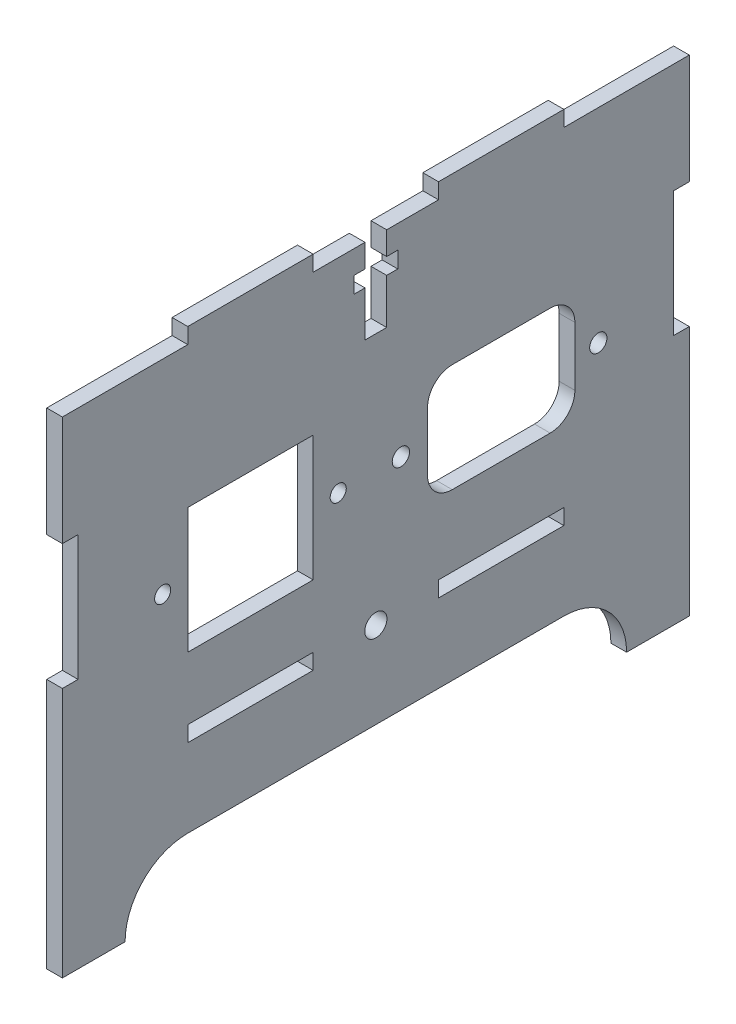
SolidWorks part; units mm, degrees
ref_plane "Front Plane" through (0, 0, 0) normal (0, 0, 1) x (1, 0, 0)
ref_plane "Top Plane" through (0, 0, 0) normal (0, 1, 0) x (1, 0, 0)
ref_plane "Right Plane" through (0, 0, 0) normal (1, 0, 0) x (0, 0, -1)
sketch "Sketch1" plane through (0, 0, 0) normal (1, 0, 0) x (0, 0, -1)
  line L1 (-63.5, 50.8) -> (63.5, 50.8)
  line L2 (-63.5, 50.8) -> (-63.5, -50.8)
  line L3 (-63.5, -50.8) -> (63.5, -50.8)
  line L4 (63.5, 50.8) -> (63.5, -50.8)
  line L5 (-63.5, 50.8) -> (63.5, -50.8) construction
  line L6 (-63.5, -50.8) -> (63.5, 50.8) construction
  point P0 (0, 0)
  dimension "D1" = 127
  dimension "D2" = 101.6
extrude "Boss-Extrude1" add sketch "Sketch1" along normal blind 3.175
sketch "Sketch2" plane through (3.175, 0, 0) normal (1, 0, 0) x (0, 0, -1)
  line L1 (-63.5, 50.8) -> (-38.1, 50.8)
  line L2 (-63.5, 50.8) -> (-63.5, 47.625)
  line L3 (-63.5, 47.625) -> (-38.1, 47.625)
  line L4 (-38.1, 50.8) -> (-38.1, 47.625)
  dimension "D1" = 25.4
  dimension "D2" = 3.175
extrude "Cut-Extrude1" cut sketch "Sketch2" against normal blind 6.35
pattern_linear "LPattern1" count 3 spacing 50.8 along (0, 0, -1) of "Cut-Extrude1"
sketch "Sketch5" plane through (3.175, 0, 0) normal (1, 0, 0) x (0, 0, -1)
  line L0 (-38.1, -50.8) -> (38.1, -50.8) construction
  line L1 (-63.5, -50.8) -> (63.5, -50.8) construction
  line L2 (-38.1, -38.1) -> (38.1, -38.1)
  line L3 (-38.1, -63.5) -> (38.1, -63.5)
  arc A0 (-38.1, -38.1) -> (-38.1, -63.5) centre (-38.1, -50.8) ccw
  arc A1 (38.1, -63.5) -> (38.1, -38.1) centre (38.1, -50.8) ccw
  point P4 (0, -50.8)
  dimension "D2" = 12.7
  dimension "D1" = 76.2
extrude "Cut-Extrude4" cut sketch "Sketch5" against normal blind 6.35
sketch "Sketch8" plane through (3.175, 0, 0) normal (1, 0, 0) x (0, 0, -1)
  line L0 (63.5, -50.8) -> (63.5, 47.625) construction
  line L1 (63.5, 25.4) -> (60.325, 25.4)
  line L2 (63.5, 25.4) -> (63.5, 0)
  line L3 (63.5, 0) -> (60.325, 0)
  line L4 (60.325, 25.4) -> (60.325, 0)
  line L5 (38.1, 50.8) -> (12.7, 50.8) construction
  dimension "D1" = 25.4
  dimension "D2" = 25.4
  dimension "D3" = 3.175
extrude "Cut-Extrude6" cut sketch "Sketch8" against normal blind 6.35
ref_plane "Plane1" through (0, 0, 0) normal (0, 0, 1) x (1, 0, 0)
sketch "Sketch9" plane through (0, 0, 0) normal (-1, 0, 0) x (0, 0, 1)
  line L0 (-63.5, -50.8) -> (-63.5, 0) construction
  line L1 (-38.1, -19.05) -> (-12.7, -19.05)
  line L2 (-38.1, -19.05) -> (-38.1, -22.225)
  line L3 (-38.1, -22.225) -> (-12.7, -22.225)
  line L4 (-12.7, -19.05) -> (-12.7, -22.225)
  line L5 (-38.1, 50.8) -> (-12.7, 50.8) construction
  point P6 (-25.4, 50.8)
  dimension "D1" = 25.4
  dimension "D2" = 3.175
  dimension "D3" = 25.4
  dimension "D4" = 69.85
extrude "Cut-Extrude7" cut sketch "Sketch9" against normal blind 6.35
pattern_linear "LPattern6" count 2 spacing 50.8 along (0, 0, 1) of "Cut-Extrude7"
sketch "Sketch16" plane through (0, 0, 0) normal (-1, 0, 0) x (0, 0, 1)
  line L0 (12.7, 47.625) -> (-12.7, 47.625) construction
  line L1 (-2.1971, 47.625) -> (2.1971, 47.625)
  line L2 (-2.1971, 47.625) -> (-2.1971, 30.48)
  line L3 (-2.1971, 30.48) -> (2.1971, 30.48)
  line L4 (2.1971, 47.625) -> (2.1971, 30.48)
  line L5 (-12.7, 47.625) -> (-12.7, 50.8) construction
  line L7 (-4.445, 42.926) -> (4.445, 42.926)
  line L8 (-4.445, 42.926) -> (-4.445, 39.624)
  line L9 (-4.445, 39.624) -> (4.445, 39.624)
  line L10 (4.445, 42.926) -> (4.445, 39.624)
  point P6 (0, 30.48)
  point P13 (0, 42.926)
  point P14 (4.445, 41.275)
  dimension "D1" = 4.3942
  dimension "D2" = 17.145
  dimension "D3" = 12.7
  dimension "D4" = 3.302
  dimension "D5" = 8.89
  dimension "D6" = 12.7
  dimension "D7" = 6.35
extrude "Cut-Extrude14" cut sketch "Sketch16" against normal blind 6.35 contours L7 L10 L9 L8 | L1 L4 L3 L2
hole_wizard "#8 Clearance Hole1" positions "Sketch18" profile "Sketch17" hole size "#8" standard "ANSI Inch"
sketch "Sketch18" plane through (0, 0, 0) normal (-1, 0, 0) x (0, 0, 1)
  line L3 (-12.7, -22.225) -> (-12.7, -19.05) construction
  line L4 (38.1, -19.05) -> (12.7, -19.05) construction
  point P0 (0, -20.6375)
  point P16 (-12.7, -20.6375)
  dimension "D1" = 12.7
  dimension "D2" = 1.5875
sketch "Sketch17" plane through (0, -20.6375, 0) normal (0, 1, 0) x (0, 0, 1)
  line L0 (0, 0) -> (0, 11.5107)
  line L1 (0, 11.5107) -> (2.2479, 10.16)
  line L2 (2.2479, 10.16) -> (2.2479, 0)
  line L5 (2.2479, 0) -> (0, 0)
  line L10 (0, 11.5107) -> (-2.2479, 10.16) construction
  line L11 (0, -6.35) -> (0, 107.95) construction
  dimension "Hole Dia." = 4.4958
  dimension "Hole Depth" = 10.16
  dimension "Drill Angle" = 118
sketch "Sketch19" plane through (0, 0, 0) normal (-1, 0, 0) x (0, 0, 1)
  line L0 (-49.53, 42.545) -> (-11.43, 42.545) construction
  line L1 (-49.53, 43.815) -> (-11.43, 43.815)
  line L2 (-49.53, 41.275) -> (-11.43, 41.275)
  line L3 (-38.1, 50.8) -> (-38.1, 47.625) construction
  line L4 (-2.1971, 47.625) -> (-12.7, 47.625) construction
  arc A0 (-49.53, 43.815) -> (-49.53, 41.275) centre (-49.53, 42.545) ccw
  arc A1 (-11.43, 41.275) -> (-11.43, 43.815) centre (-11.43, 42.545) ccw
  point P2 (-30.48, 42.545)
  point P7 (-30.48, 43.815)
  dimension "D2" = 1.27
  dimension "D1" = 38.1
  dimension "D3" = 7.62
  dimension "D4" = 3.81
extrude "Cut-Extrude15" [suppressed] cut sketch "Sketch19" against normal blind 6.35
mirror "Mirror2" [suppressed] about plane through (0, 0, 0) normal (0, 0, 1)
pattern_linear "LPattern7" [suppressed] count 5 spacing 5.08 of bodies 127
sketch "Sketch20" plane through (0, 0, 0) normal (-1, 0, 0) x (0, 0, 1)
  line L0 (-38.1, 50.8) -> (-12.7, 50.8) construction
  line L1 (-35.3225, 17.3101) -> (-15.4775, 17.3101)
  line L2 (-40.3225, 12.3101) -> (-40.3225, 0.3899)
  line L3 (-35.3225, -4.6101) -> (-15.4775, -4.6101)
  line L4 (-10.4775, 12.3101) -> (-10.4775, 0.3899)
  line L5 (-63.5, -50.8) -> (-63.5, 0) construction
  circle A0 centre (-45.0725, 6.35) radius 1.75
  circle A1 centre (-5.0725, 6.35) radius 1.75
  arc A2 (-40.3225, 0.3899) -> (-35.3225, -4.6101) centre (-35.3225, 0.3899) ccw
  arc A3 (-15.4775, 17.3101) -> (-10.4775, 12.3101) centre (-15.4775, 12.3101) cw
  arc A4 (-15.4775, -4.6101) -> (-10.4775, 0.3899) centre (-15.4775, 0.3899) ccw
  arc A5 (-40.3225, 12.3101) -> (-35.3225, 17.3101) centre (-35.3225, 12.3101) cw
  point P8 (-25.4, 17.3101)
  point P13 (-40.3225, 6.35)
  point P18 (-10.4775, 17.3101)
  point P21 (-10.4775, -4.6101)
  point P24 (-40.3225, 17.3101)
  dimension "D1" = 3.5
  dimension "D2" = 3.5
  dimension "D10" = 5
  dimension "D11" = 5
  dimension "D12" = 5
  dimension "D13" = 5
  dimension "D3" = 40
  dimension "D4" = 29.845
  dimension "D5" = 21.9202
  dimension "D6" = 38.1
  dimension "D7" = 44.45
extrude "Cut-Extrude16" cut sketch "Sketch20" against normal blind 7.62
sketch "Sketch25" plane through (0, 0, 0) normal (-1, 0, 0) x (0, 0, 1)
  line L0 (12.7, -19.05) -> (12.7, -22.225) construction
  line L1 (12.7, -6.35) -> (38.1, -6.35)
  line L2 (12.7, -6.35) -> (12.7, 19.05)
  line L3 (12.7, 19.05) -> (38.1, 19.05)
  line L4 (38.1, -6.35) -> (38.1, 19.05)
  line L6 (12.7, 50.8) -> (38.1, 50.8) construction
  point P6 (12.7, 6.35)
  dimension "D1" = 25.4
  dimension "D2" = 25.4
  dimension "D3" = 44.45
extrude "Cut-Extrude20" cut sketch "Sketch25" against normal blind 7.62
mirror "Mirror3" about plane through (0, 0, 0) normal (0, 0, 1) of "Cut-Extrude6"
hole_wizard "#4 Clearance Hole1" positions "Sketch27" profile "Sketch26" hole size "#4" standard "ANSI Inch"
sketch "Sketch27" plane through (3.175, 0, 0) normal (1, 0, 0) x (0, 0, -1)
  line L0 (-38.1, 19.05) -> (-38.1, -6.35) construction
  line L1 (-12.7, -6.35) -> (-12.7, 19.05) construction
  point P0 (-43.18, 6.35)
  point P2 (-7.62, 6.35)
  dimension "D1" = 5.08
  dimension "D2" = 5.08
sketch "Sketch26" plane through (3.175, 6.35, 43.18) normal (0, 1, 0) x (0, 0, -1)
  line L0 (0, 0) -> (0, 11.1406)
  line L1 (0, 11.1406) -> (1.6319, 10.16)
  line L2 (1.6319, 10.16) -> (1.6319, 0)
  line L5 (1.6319, 0) -> (0, 0)
  line L10 (0, 11.1406) -> (-1.6319, 10.16) construction
  line L11 (0, -6.35) -> (0, 107.95) construction
  dimension "Hole Dia." = 3.2639
  dimension "Hole Depth" = 10.16
  dimension "Drill Angle" = 118
